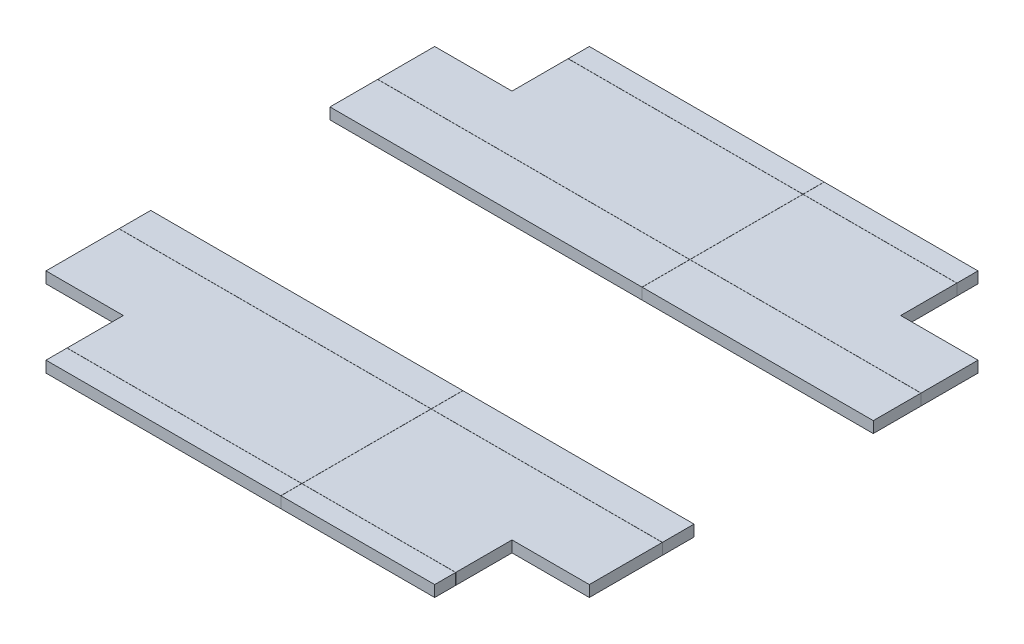
SolidWorks part; units mm, degrees
material "Glass"
ref_plane "Front" through (0, 0, 0) normal (0, 0, 1) x (1, 0, 0)
ref_plane "Top" through (0, 0, 0) normal (0, 1, 0) x (1, 0, 0)
ref_plane "Right" through (0, 0, 0) normal (1, 0, 0) x (0, 0, -1)
sketch "Sketch1" plane through (0, 0, 0) normal (0, 1, 0) x (1, 0, 0)
  line L1 (-2454.275, 2454.275) -> (2454.275, 2454.275)
  line L2 (-2454.275, 2454.275) -> (-2454.275, -2454.275)
  line L3 (-2454.275, -2454.275) -> (2454.275, -2454.275)
  line L4 (2454.275, 2454.275) -> (2454.275, -2454.275)
  line L5 (-2454.275, 2454.275) -> (2454.275, -2454.275) construction
  line L6 (-2454.275, -2454.275) -> (2454.275, 2454.275) construction
  point P0 (0, 0)
  dimension "D1" = 4908.55
  dimension "D2" = 4908.55
extrude "Boss-Extrude1" add sketch "Sketch1" along normal blind 101.6
sketch "Sketch2" plane through (0, 101.6, 0) normal (0, 1, 0) x (1, 0, 0)
  line L0 (-2454.275, 2454.275) -> (-2454.275, -2454.275) construction
  line L1 (2454.275, -809.625) -> (-2454.275, -809.625)
  line L2 (2454.275, -809.625) -> (2454.275, 809.625)
  line L3 (2454.275, 809.625) -> (-2454.275, 809.625)
  line L4 (-2454.275, -809.625) -> (-2454.275, 809.625)
  line L5 (2454.275, -809.625) -> (-2454.275, 809.625) construction
  line L6 (2454.275, 809.625) -> (-2454.275, -809.625) construction
  point P0 (0, 0)
  dimension "D1" = 1619.25
extrude "Cut-Extrude1" cut sketch "Sketch2" against normal through all
sketch "Sketch3" plane through (0, 101.6, 0) normal (0, 1, 0) x (1, 0, 0)
  line L1 (-2454.275, -2454.275) -> (-1755.775, -2454.275)
  line L2 (-2454.275, -2454.275) -> (-2454.275, -1755.775)
  line L3 (-2454.275, -1755.775) -> (-1755.775, -1755.775)
  line L4 (-1755.775, -2454.275) -> (-1755.775, -1755.775)
  line L5 (2454.275, -2454.275) -> (1755.775, -2454.275)
  line L6 (2454.275, -2454.275) -> (2454.275, -1755.775)
  line L7 (2454.275, -1755.775) -> (1755.775, -1755.775)
  line L8 (1755.775, -2454.275) -> (1755.775, -1755.775)
  line L9 (-2454.275, 2454.275) -> (-1755.775, 2454.275)
  line L10 (-2454.275, 2454.275) -> (-2454.275, 1755.775)
  line L11 (-2454.275, 1755.775) -> (-1755.775, 1755.775)
  line L12 (-1755.775, 2454.275) -> (-1755.775, 1755.775)
  line L13 (2454.275, 2454.275) -> (1755.775, 2454.275)
  line L14 (2454.275, 2454.275) -> (2454.275, 1755.775)
  line L15 (2454.275, 1755.775) -> (1755.775, 1755.775)
  line L16 (1755.775, 2454.275) -> (1755.775, 1755.775)
  dimension "D1" = 698.5
extrude "Cut-Extrude2" cut sketch "Sketch3" against normal through all
sketch "Sketch4" plane through (0, 101.6, 0) normal (0, 1, 0) x (1, 0, 0)
  line L0 (-1755.775, -2263.775) -> (1755.775, -2263.775)
  line L1 (-1755.775, -2454.275) -> (-1755.775, -1755.775) construction
  line L2 (1755.775, -1755.775) -> (1755.775, -2454.275) construction
  line L3 (-1755.775, -2454.275) -> (1755.775, -2454.275) construction
  line L4 (-2454.275, -1095.375) -> (2461.4866, -1095.375)
  line L5 (-2454.275, -809.625) -> (-2454.275, -1755.775) construction
  line L6 (-2454.275, -809.625) -> (2454.275, -809.625) construction
  line L7 (-1755.775, 2263.775) -> (1755.775, 2263.775)
  line L8 (-1755.775, 1755.775) -> (-1755.775, 2454.275) construction
  line L9 (1755.775, 2454.275) -> (1755.775, 1755.775) construction
  line L10 (-2454.275, 1241.425) -> (2454.275, 1241.425)
  line L11 (-2454.275, 1755.775) -> (-2454.275, 809.625) construction
  line L12 (2454.275, 809.625) -> (2454.275, 1755.775) construction
  line L13 (1755.775, 2454.275) -> (-1755.775, 2454.275) construction
  line L14 (2454.275, 809.625) -> (-2454.275, 809.625) construction
  dimension "D1" = 190.5
  dimension "D2" = 1168.4
  dimension "D3" = 285.75
  dimension "D4" = 190.5
  dimension "D5" = 1022.35
  dimension "D6" = 431.8
extrude "Cut-Extrude-Thin1" cut sketch "Sketch4" against normal through all thin thin type one direction wall 1.27
sketch "Sketch5" plane through (0, 101.6, 0) normal (0, 1, 0) x (1, 0, 0)
  line L0 (365.125, -2454.275) -> (365.125, 2454.275)
  line L1 (-1755.775, -2454.275) -> (1755.775, -2454.275) construction
  line L2 (1755.775, 2454.275) -> (-1755.775, 2454.275) construction
  line L3 (2454.275, -1755.775) -> (2454.275, -1096.645) construction
  line L4 (-2454.275, -1096.645) -> (-2454.275, -1755.775) construction
  dimension "D1" = 2089.15
  dimension "D2" = 2819.4
extrude "Cut-Extrude-Thin2" cut sketch "Sketch5" against normal through all and the other way through all thin thin type one direction wall 1.27
